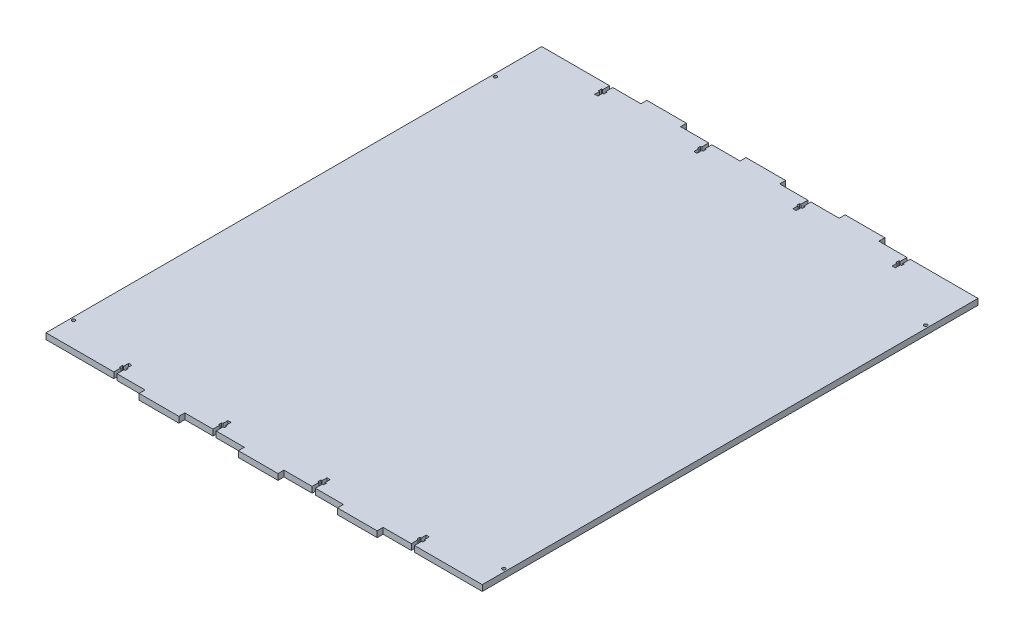
SolidWorks part; units mm, degrees
ref_plane "Front Plane" through (0, 0, 0) normal (0, 0, 1) x (1, 0, 0)
ref_plane "Top Plane" through (0, 0, 0) normal (0, 1, 0) x (1, 0, 0)
ref_plane "Right Plane" through (0, 0, 0) normal (1, 0, 0) x (0, 0, -1)
sketch "Sketch1" plane through (0, 0, 0) normal (0, 1, 0) x (1, 0, 0)
  line L1 (-220, -250) -> (220, -250)
  line L2 (-220, -250) -> (-220, 250)
  line L3 (-220, 250) -> (220, 250)
  line L4 (220, -250) -> (220, 250)
  line L5 (-220, -250) -> (220, 250) construction
  line L6 (-220, 250) -> (220, -250) construction
  point P0 (0, 0)
  dimension "D1" = 440
  dimension "D2" = 500
extrude "Boss-Extrude1" add sketch "Sketch1" along normal blind 6
sketch "Sketch2" plane through (0, 0, 0) normal (0, -1, 0) x (1, 0, 0)
  line L14 (0, 0) -> (0, 133.2527) construction
  line L15 (0, 0) -> (-145.1849, 0) construction
  line L40 (-148.4, 256) -> (-151.6, 256) construction
  line L41 (-148.4, 256) -> (-151.6, 256) construction
  line L42 (-48.4, 256) -> (-51.6, 256) construction
  line L43 (-48.4, 256) -> (-51.6, 256) construction
  line L44 (-148.4, 256) -> (-51.6, 256) construction
  line L45 (-220, 250) -> (220, 250) construction
  line L46 (-120, 256) -> (-80, 256)
  line L47 (-120, 256) -> (-120, 250)
  line L48 (-120, 250) -> (-80, 250)
  line L49 (-80, 256) -> (-80, 250)
  line L50 (-20, 250) -> (20, 250)
  line L51 (20, 256) -> (20, 250)
  line L52 (-20, 256) -> (20, 256)
  line L53 (-20, 256) -> (-20, 250)
  line L54 (80, 250) -> (120, 250)
  line L55 (120, 256) -> (120, 250)
  line L56 (80, 256) -> (120, 256)
  line L57 (80, 256) -> (80, 250)
  line L58 (120, -256) -> (120, -250)
  line L59 (80, -250) -> (120, -250)
  line L60 (80, -256) -> (120, -256)
  line L61 (80, -256) -> (80, -250)
  line L62 (20, -256) -> (20, -250)
  line L63 (-20, -256) -> (20, -256)
  line L64 (-20, -250) -> (20, -250)
  line L65 (-20, -256) -> (-20, -250)
  line L66 (-120, -250) -> (-80, -250)
  line L67 (-120, -256) -> (-120, -250)
  line L68 (-120, -256) -> (-80, -256)
  line L69 (-80, -256) -> (-80, -250)
  point P50 (-100, 256)
  dimension "D3" = 40
  dimension "D4" = 3
extrude "Boss-Extrude2" add sketch "Sketch2" against normal blind 6
sketch "Sketch3" plane through (0, 0, 0) normal (0, -1, 0) x (1, 0, 0)
  line L1 (214, 226.85) -> (220, 223.65) construction
  line L2 (214, -198.65) -> (220, -201.85) construction
  line L6 (214, 226.85) -> (214, 223.65)
  line L7 (214, 223.65) -> (220, 223.65)
  line L8 (220, 223.65) -> (220, 226.85)
  line L9 (220, 226.85) -> (214, 226.85)
  line L10 (214, 226.85) -> (214, 223.65) construction
  line L11 (214, 223.65) -> (220, 223.65) construction
  line L12 (220, 223.65) -> (220, 226.85) construction
  line L13 (220, 226.85) -> (214, 226.85) construction
  line L14 (214, -198.65) -> (214, -201.85)
  line L15 (214, -201.85) -> (220, -201.85)
  line L16 (220, -201.85) -> (220, -198.65)
  line L17 (220, -198.65) -> (214, -198.65)
  line L18 (214, -198.65) -> (214, -201.85) construction
  line L19 (214, -201.85) -> (220, -201.85) construction
  line L20 (220, -201.85) -> (220, -198.65) construction
  line L21 (220, -198.65) -> (214, -198.65) construction
  line L86 (0, 0) -> (0, 128.8409) construction
  line L166 (-151.6, -256) -> (-148.4, -256) construction
  line L167 (-151.6, -256) -> (-148.4, -256) construction
  line L168 (-150, -256) -> (-150, -234.6121) construction
  line L169 (-120, -250) -> (-220, -250) construction
  line L170 (-151.6, -235) -> (-148.4, -235)
  line L171 (-151.6, -235) -> (-151.6, -240)
  line L172 (-151.6, -250) -> (-148.4, -250)
  line L173 (-148.4, -235) -> (-148.4, -240)
  line L174 (-151.6, -235) -> (-148.4, -250) construction
  line L175 (-151.6, -250) -> (-148.4, -235) construction
  line L176 (-148.4, -243) -> (-147.2, -243)
  line L177 (-152.8, -243) -> (-151.6, -243)
  line L178 (-152.8, -243) -> (-152.8, -240)
  line L179 (-152.8, -240) -> (-151.6, -240)
  line L180 (-147.2, -243) -> (-147.2, -240)
  line L181 (-152.8, -243) -> (-147.2, -240) construction
  line L182 (-152.8, -240) -> (-147.2, -243) construction
  line L183 (-151.6, -243) -> (-151.6, -250)
  line L184 (-148.4, -243) -> (-148.4, -250)
  line L185 (-148.4, -240) -> (-147.2, -240)
  line L186 (-51.6, -235) -> (-48.4, -235)
  line L187 (-51.6, -235) -> (-51.6, -240)
  line L188 (-51.6, -250) -> (-48.4, -250)
  line L189 (-48.4, -235) -> (-48.4, -240)
  line L190 (-48.4, -243) -> (-47.2, -243)
  line L191 (-52.8, -243) -> (-51.6, -243)
  line L192 (-52.8, -243) -> (-52.8, -240)
  line L193 (-52.8, -240) -> (-51.6, -240)
  line L194 (-47.2, -243) -> (-47.2, -240)
  line L195 (-51.6, -243) -> (-51.6, -250)
  line L196 (-48.4, -243) -> (-48.4, -250)
  line L197 (-48.4, -240) -> (-47.2, -240)
  line L198 (-51.6, -235) -> (-48.4, -250) construction
  line L199 (-51.6, -250) -> (-48.4, -235) construction
  line L200 (-52.8, -243) -> (-47.2, -240) construction
  line L201 (-52.8, -240) -> (-47.2, -243) construction
  line L202 (48.4, -235) -> (51.6, -235)
  line L203 (48.4, -235) -> (48.4, -240)
  line L204 (48.4, -250) -> (51.6, -250)
  line L205 (51.6, -235) -> (51.6, -240)
  line L206 (51.6, -243) -> (52.8, -243)
  line L207 (47.2, -243) -> (48.4, -243)
  line L208 (47.2, -243) -> (47.2, -240)
  line L209 (47.2, -240) -> (48.4, -240)
  line L210 (52.8, -243) -> (52.8, -240)
  line L211 (48.4, -243) -> (48.4, -250)
  line L212 (51.6, -243) -> (51.6, -250)
  line L213 (51.6, -240) -> (52.8, -240)
  line L214 (48.4, -235) -> (51.6, -250) construction
  line L215 (48.4, -250) -> (51.6, -235) construction
  line L216 (47.2, -243) -> (52.8, -240) construction
  line L217 (47.2, -240) -> (52.8, -243) construction
  line L218 (148.4, -235) -> (151.6, -235)
  line L219 (148.4, -235) -> (148.4, -240)
  line L220 (148.4, -250) -> (151.6, -250)
  line L221 (151.6, -235) -> (151.6, -240)
  line L222 (151.6, -243) -> (152.8, -243)
  line L223 (147.2, -243) -> (148.4, -243)
  line L224 (147.2, -243) -> (147.2, -240)
  line L225 (147.2, -240) -> (148.4, -240)
  line L226 (152.8, -243) -> (152.8, -240)
  line L227 (148.4, -243) -> (148.4, -250)
  line L228 (151.6, -243) -> (151.6, -250)
  line L229 (151.6, -240) -> (152.8, -240)
  line L230 (148.4, -235) -> (151.6, -250) construction
  line L231 (148.4, -250) -> (151.6, -235) construction
  line L232 (147.2, -243) -> (152.8, -240) construction
  line L233 (147.2, -240) -> (152.8, -243) construction
  line L235 (147.2, 240) -> (152.8, 243) construction
  line L236 (147.2, 243) -> (152.8, 240) construction
  line L237 (148.4, 250) -> (151.6, 235) construction
  line L238 (148.4, 235) -> (151.6, 250) construction
  line L239 (47.2, 240) -> (52.8, 243) construction
  line L240 (47.2, 243) -> (52.8, 240) construction
  line L241 (48.4, 250) -> (51.6, 235) construction
  line L242 (48.4, 235) -> (51.6, 250) construction
  line L243 (-52.8, 240) -> (-47.2, 243) construction
  line L244 (-52.8, 243) -> (-47.2, 240) construction
  line L245 (-51.6, 250) -> (-48.4, 235) construction
  line L246 (-51.6, 235) -> (-48.4, 250) construction
  line L247 (-152.8, 240) -> (-147.2, 243) construction
  line L248 (-152.8, 243) -> (-147.2, 240) construction
  line L249 (-151.6, 250) -> (-148.4, 235) construction
  line L250 (-151.6, 235) -> (-148.4, 250) construction
  line L251 (151.6, 240) -> (152.8, 240)
  line L252 (151.6, 243) -> (151.6, 250)
  line L253 (148.4, 243) -> (148.4, 250)
  line L254 (152.8, 243) -> (152.8, 240)
  line L255 (147.2, 240) -> (148.4, 240)
  line L256 (147.2, 243) -> (147.2, 240)
  line L257 (147.2, 243) -> (148.4, 243)
  line L258 (151.6, 243) -> (152.8, 243)
  line L259 (151.6, 235) -> (151.6, 240)
  line L260 (148.4, 250) -> (151.6, 250)
  line L261 (148.4, 235) -> (148.4, 240)
  line L262 (148.4, 235) -> (151.6, 235)
  line L263 (51.6, 240) -> (52.8, 240)
  line L264 (51.6, 243) -> (51.6, 250)
  line L265 (48.4, 243) -> (48.4, 250)
  line L266 (52.8, 243) -> (52.8, 240)
  line L267 (47.2, 240) -> (48.4, 240)
  line L268 (47.2, 243) -> (47.2, 240)
  line L269 (47.2, 243) -> (48.4, 243)
  line L270 (51.6, 243) -> (52.8, 243)
  line L271 (51.6, 235) -> (51.6, 240)
  line L272 (48.4, 250) -> (51.6, 250)
  line L273 (48.4, 235) -> (48.4, 240)
  line L274 (48.4, 235) -> (51.6, 235)
  line L275 (-48.4, 240) -> (-47.2, 240)
  line L276 (-48.4, 243) -> (-48.4, 250)
  line L277 (-51.6, 243) -> (-51.6, 250)
  line L278 (-47.2, 243) -> (-47.2, 240)
  line L279 (-52.8, 240) -> (-51.6, 240)
  line L280 (-52.8, 243) -> (-52.8, 240)
  line L281 (-52.8, 243) -> (-51.6, 243)
  line L282 (-48.4, 243) -> (-47.2, 243)
  line L283 (-48.4, 235) -> (-48.4, 240)
  line L284 (-51.6, 250) -> (-48.4, 250)
  line L285 (-51.6, 235) -> (-51.6, 240)
  line L286 (-51.6, 235) -> (-48.4, 235)
  line L287 (-148.4, 240) -> (-147.2, 240)
  line L288 (-148.4, 243) -> (-148.4, 250)
  line L289 (-151.6, 243) -> (-151.6, 250)
  line L290 (-147.2, 243) -> (-147.2, 240)
  line L291 (-152.8, 240) -> (-151.6, 240)
  line L292 (-152.8, 243) -> (-152.8, 240)
  line L293 (-152.8, 243) -> (-151.6, 243)
  line L294 (-148.4, 243) -> (-147.2, 243)
  line L295 (-148.4, 235) -> (-148.4, 240)
  line L296 (-151.6, 250) -> (-148.4, 250)
  line L297 (-151.6, 235) -> (-151.6, 240)
  line L298 (-151.6, 235) -> (-148.4, 235)
  circle A0 centre (217, 225.25) radius 1.6
  circle A1 centre (217, -200.25) radius 1.6
  circle A2 centre (-217, -200.25) radius 1.6
  circle A3 centre (-217, 225.25) radius 1.6
  point P154 (-150, -242.5)
  point P161 (-150, -241.5)
  point P171 (-50, -242.5)
  point P176 (-50, -241.5)
  point P185 (50, -242.5)
  point P190 (50, -241.5)
  point P199 (150, -242.5)
  point P204 (150, -241.5)
  point P261 (150, 241.5)
  point P262 (150, 242.5)
  point P263 (50, 241.5)
  point P264 (50, 242.5)
  point P265 (-50, 241.5)
  point P266 (-50, 242.5)
  point P267 (-150, 241.5)
  point P268 (-150, 242.5)
  line M6 (220, 250) -> (120, 250)
  line M10 (80, 250) -> (20, 250)
  line M14 (-20, 250) -> (-80, 250)
  line M18 (-120, 250) -> (-220, 250)
  line M20 (-220, -250) -> (-120, -250)
  line M24 (-80, -250) -> (-20, -250)
  line M28 (20, -250) -> (80, -250)
  line M32 (120, -250) -> (220, -250)
  dimension "D1" = 0
  dimension "D2" = 0
  dimension "D6" = 15
  dimension "D7" = 5.6
  dimension "D8" = 7
  dimension "D9" = 4
extrude "Cut-Extrude1" cut sketch "Sketch3" against normal through all contours L185 L173 L170 L171 L179 L178 L177 L183 L184 L176 L180 M20 | L197 L189 L186 L187 L193 L192 L191 L195 L196 L190 L194 M24 | L213 L205 L202 L203 L209 L208 L207 L211 L212 L206 L210 M28 | L229 L221 L218 L219 L225 L224 L223 L227 L228 L222 L226 M32 | L297 L298 L295 L287 L290 L294 L288 L289 L293 L292 L291 M18 | L285 L286 L283 L275 L278 L282 L276 L277 L281 L280 L279 M14 | L273 L274 L271 L263 L266 L270 L264 L265 L269 L268 L267 M10 | L261 L262 L259 L251 L254 L258 L252 L253 L257 L256 L255 M6 | A1 | A0 | A3 | A2
